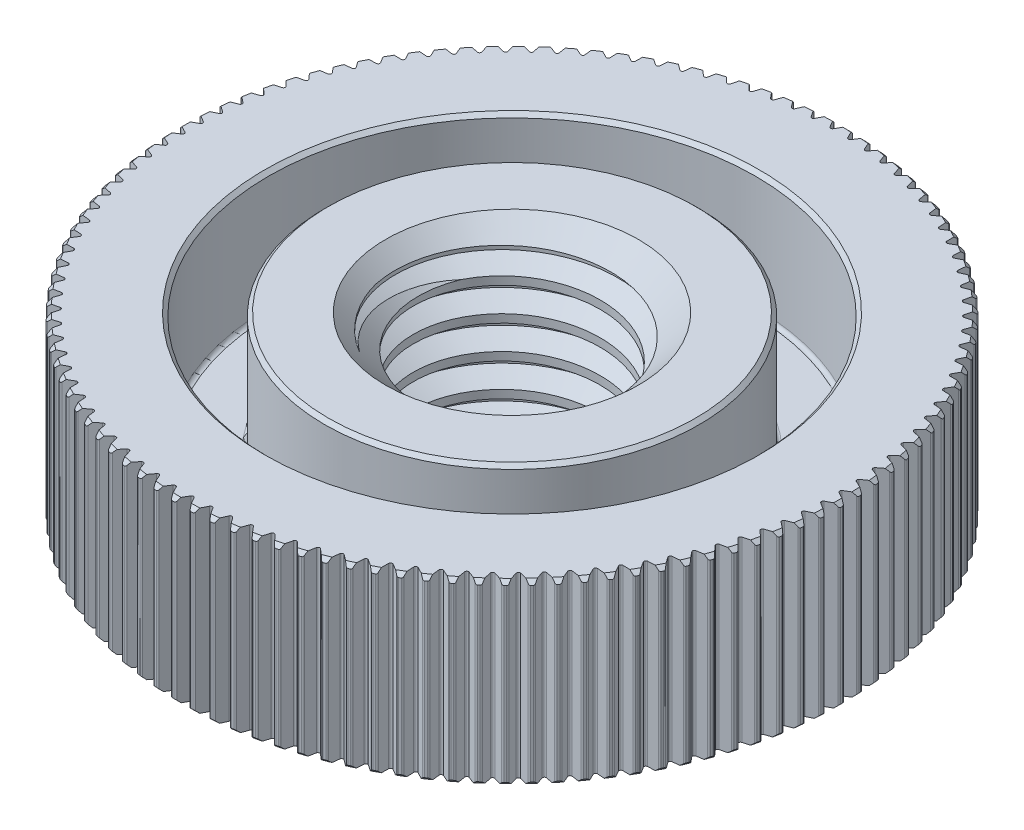
SolidWorks part; units mm, degrees
material "ABS"
ref_plane "Front Plane" through (0, 0, 0) normal (0, 0, 1) x (1, 0, 0)
ref_plane "Top Plane" through (0, 0, 0) normal (0, 1, 0) x (1, 0, 0)
ref_plane "Right Plane" through (0, 0, 0) normal (1, 0, 0) x (0, 0, -1)
sketch "Profile Sketch" plane through (0, 0, 0) normal (0, 1, 0) x (1, 0, 0)
  circle A0 centre (0, 0) radius 17.6
  circle A1 centre (0, 0) radius 5
  dimension "D1" = 35.2
  dimension "D2" = 10
extrude "Body" add sketch "Profile Sketch" against normal blind 9.5
sketch "Cut Out Sketch" plane through (0, 0, 0) normal (0, 1, 0) x (1, 0, 0)
  circle A0 centre (0, 0) radius 13
  circle A1 centre (0, 0) radius 10
  dimension "D1" = 26
  dimension "D2" = 20
extrude "Cut Out" cut sketch "Cut Out Sketch" against normal blind 6.5
fillet "Production Fillet" radius 0.2 2 edges at (0, -6.5, 13) (0, -6.5, 10)
chamfer "Aesthetic Chamfer" distance 0.2 angle 45 5 edges at (0, 0, 17.6) (0, 0, 13) (0, 0, 10) (0, -9.5, 17.6) (0, -9.5, 5)
chamfer "Thread In Chamfer" distance 1.75 angle 45 1 edges at (0, 0, 5)
sketch "Tooth Profile" plane through (0, 0, 0) normal (0, 1, 0) x (1, 0, 0)
  line L0 (-0.3608, 17.5443) -> (-0.0866, 17.0693)
  line L1 (0.3608, 17.5443) -> (0.0866, 17.0693)
  line L2 (-0.4474, 17.4943) -> (0.4474, 17.4943) construction
  line L3 (-0.45, 17.5942) -> (-0.45, 17.8942)
  line L4 (-0.45, 17.8942) -> (0.45, 17.8942)
  line L5 (0.45, 17.8942) -> (0.45, 17.5942)
  arc A0 (-0.0866, 17.0693) -> (0.0866, 17.0693) centre (0, 17.1193) ccw
  arc A1 (0.45, 17.5942) -> (0.3608, 17.5443) centre (0.4474, 17.4943) ccw
  arc A2 (-0.3608, 17.5443) -> (-0.45, 17.5942) centre (-0.4474, 17.4943) ccw
  circle A5 centre (0, 0) radius 17.6 construction
  point P5 (-0.45, 17.5942)
  point P11 (0, 17.4943)
  point P12 (0.45, 17.5942)
  dimension "D1" = 60
  dimension "D2" = 0.1
  dimension "D3" = 0.9
  dimension "D4" = 0.3
extrude "Tooth Cut" cut sketch "Tooth Profile" against normal through all
pattern_circular "Tooth Pattern" count 110 over 360 about axis through (0, -9.5, 0) along (0, 1, 0) of "Tooth Cut"
thread "M12x1.75" pitch 1.75 method cut profile "Thread Profile1" start angle 292.5, offset 3.5, length 12, pitch 1.75, diameter 10
ref_plane "Plane1" through (-1.9134, 1.75, 4.6194) normal (0.9239, 0, 0.3827) x (-0.3827, 0, 0.9239)
sketch "Thread Profile1" plane through (-1.9134, 1.75, 4.6194) normal (0.9239, 0, 0.3827) x (-0.3827, 0, 0.9239)
  line L0 (0, 0) -> (0, 1.75) construction
  line L1 (0, 0) -> (0.9472, 0.5469)
  line L2 (0.9472, 0.5469) -> (0.9472, 0.7656)
  line L3 (0.9472, 0.7656) -> (0, 1.3125)
  line L4 (0.9472, 0.6562) -> (0, 0.6562) construction
  line L11 (0, 0) -> (0, 1.3125)
  point P2 (0, 0)
  dimension "Pitch" = 1.75
  dimension "Profile_Angle" = 60
  dimension "Profile_Land" = 0.2188
  dimension "Profile_Height" = 0.9472
